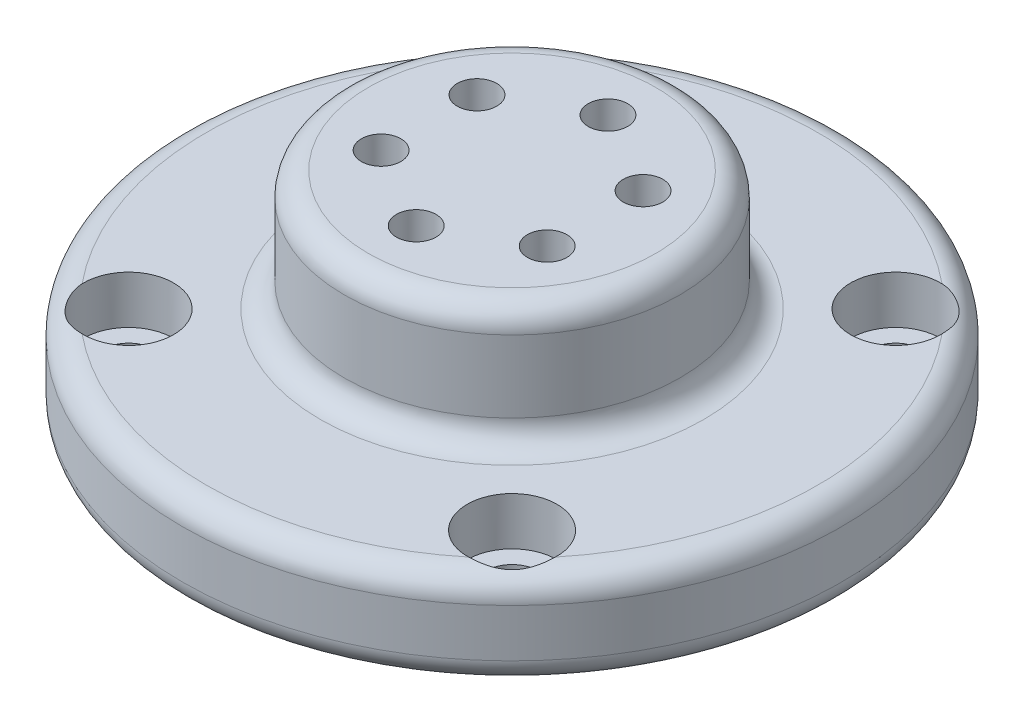
SolidWorks part; units mm, degrees
ref_plane "Front Plane" through (0, 0, 0) normal (0, 0, 1) x (1, 0, 0)
ref_plane "Top Plane" through (0, 0, 0) normal (0, 1, 0) x (1, 0, 0)
ref_plane "Right Plane" through (0, 0, 0) normal (1, 0, 0) x (0, 0, -1)
sketch "Sketch1" plane through (0, 0, 0) normal (0, 1, 0) x (1, 0, 0)
  circle A0 centre (-6.9282, 4) radius 1.65
  circle A1 centre (0, 8) radius 1.65
  circle A2 centre (6.9282, 4) radius 1.65
  circle A3 centre (6.9282, -4) radius 1.65
  circle A4 centre (0, -8) radius 1.65
  circle A5 centre (-6.9282, -4) radius 1.65
  circle A6 centre (0, 0) radius 8 construction
  circle A7 centre (-16, 16) radius 2.15
  circle A8 centre (16, 16) radius 2.15
  circle A9 centre (16, -16) radius 2.15
  circle A10 centre (-16, -16) radius 2.15
  circle A11 centre (0, 0) radius 27.5
  point P14 (0, 0)
  point P27 (0, 0)
  dimension "D2" = 16
  dimension "D3" = 3.3
  dimension "D5" = 32
  dimension "D6" = 4.3
  dimension "D7" = 55
  dimension "D1" = 6
  dimension "D4" = 4
extrude "Boss-Extrude1" add sketch "Sketch1" along normal blind 8
sketch "Sketch2" plane through (0, 8, 0) normal (0, 1, 0) x (1, 0, 0)
  circle A0 centre (0, 0) radius 14
  circle A1 centre (-6.9282, -4) radius 1.65 construction
  circle A2 centre (0, -8) radius 1.65 construction
  circle A3 centre (6.9282, -4) radius 1.65 construction
  circle A4 centre (6.9282, 4) radius 1.65 construction
  circle A5 centre (0, 8) radius 1.65 construction
  circle A6 centre (-6.9282, 4) radius 1.65 construction
  circle A7 centre (-6.9282, -4) radius 1.65
  circle A8 centre (0, -8) radius 1.65
  circle A9 centre (6.9282, -4) radius 1.65
  circle A10 centre (6.9282, 4) radius 1.65
  circle A11 centre (0, 8) radius 1.65
  circle A12 centre (-6.9282, 4) radius 1.65
  dimension "D1" = 28
extrude "Boss-Extrude2" add sketch "Sketch2" along normal blind 10
sketch "Sketch3" plane through (0, 0, 0) normal (0, -1, 0) x (1, 0, 0)
  circle A0 centre (0, 8) radius 3
  circle A1 centre (6.9282, 4) radius 3
  circle A2 centre (6.9282, -4) radius 3
  circle A3 centre (0, -8) radius 3
  circle A4 centre (-6.9282, -4) radius 3
  circle A5 centre (-6.9282, 4) radius 3
  circle A6 centre (-6.9282, 4) radius 1.65 construction
  point P4 (0, 0)
  point P15 (0, 0)
  dimension "D2" = 6
  dimension "D1" = 6
extrude "Cut-Extrude1" cut sketch "Sketch3" against normal blind 12
sketch "Sketch4" plane through (0, 8, 0) normal (0, 1, 0) x (1, 0, 0)
  circle A0 centre (-16, 16) radius 3.75
  circle A1 centre (16, 16) radius 3.75
  circle A2 centre (16, -16) radius 3.75
  circle A3 centre (-16, -16) radius 3.75
  circle A4 centre (16, 16) radius 2.15 construction
  point P12 (0, 0)
  dimension "D1" = 7.5
  dimension "D2" = 4
extrude "Cut-Extrude2" cut sketch "Sketch4" against normal blind 4
fillet "Fillet1" radius 2 4 edges at (0, 8, 14) (0, 18, 14) (0, 0, 27.5) (0, 8, 27.5)
